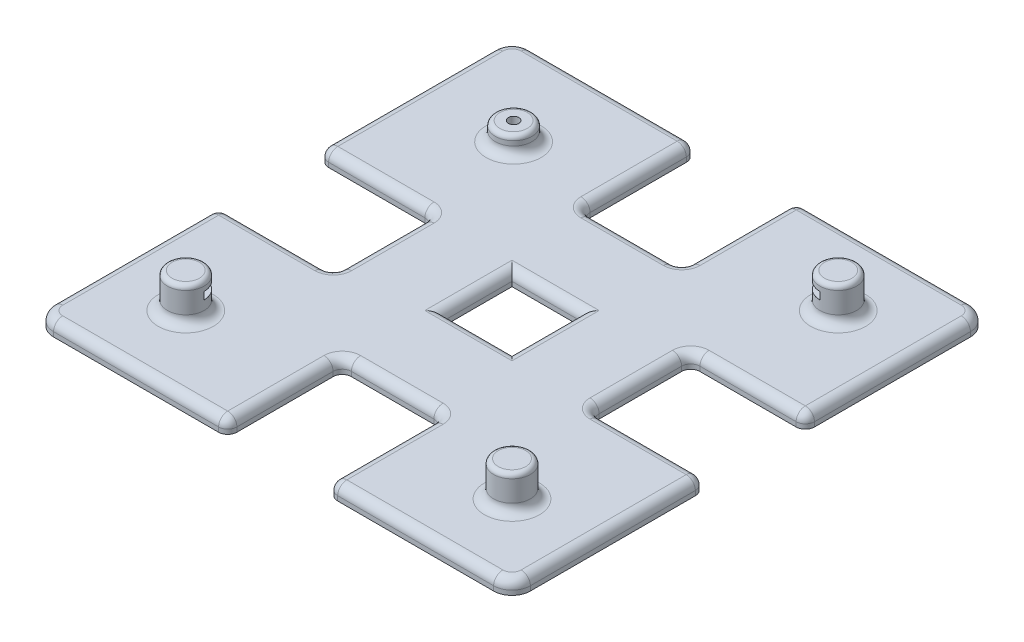
SolidWorks part; units mm, degrees
ref_plane "Front Plane" through (0, 0, 0) normal (0, 0, 1) x (1, 0, 0)
ref_plane "Top Plane" through (0, 0, 0) normal (0, 1, 0) x (1, 0, 0)
ref_plane "Right Plane" through (0, 0, 0) normal (1, 0, 0) x (0, 0, -1)
sketch "Sketch1" plane through (0, 0, 0) normal (0, 1, 0) x (1, 0, 0)
  line L0 (0, 51.97) -> (0, -51.97) construction
  line L1 (-51.97, 51.97) -> (51.97, 51.97)
  line L2 (-51.97, 51.97) -> (-51.97, -51.97)
  line L3 (-51.97, -51.97) -> (51.97, -51.97)
  line L4 (51.97, 51.97) -> (51.97, -51.97)
  line L5 (-51.97, 51.97) -> (51.97, -51.97) construction
  line L6 (-51.97, -51.97) -> (51.97, 51.97) construction
  line L7 (-51.97, 0) -> (51.97, 0) construction
  circle A0 centre (-31.7, 32.05) radius 1.1303
  circle A1 centre (31.7, 32.05) radius 1.1303 construction
  circle A2 centre (31.7, -32.05) radius 1.1303 construction
  circle A3 centre (-31.7, -32.05) radius 1.1303 construction
  point P0 (0, 0)
  dimension "D2" = 2.2606
  dimension "D1" = 103.94
  dimension "D3" = 63.4
  dimension "D4" = 64.1
extrude "Boss-Extrude1" add sketch "Sketch1" along normal blind 3
sketch "Sketch6" plane through (0, 3, 0) normal (0, 1, 0) x (1, 0, 0)
  line L0 (0, 51.97) -> (0, -51.97) construction
  line L1 (51.97, 51.97) -> (-51.97, 51.97) construction
  line L2 (-51.97, -51.97) -> (51.97, -51.97) construction
  line L3 (-51.97, 0) -> (51.97, 0) construction
  line L4 (-51.97, 51.97) -> (-51.97, -51.97) construction
  line L5 (51.97, -51.97) -> (51.97, 51.97) construction
  line L7 (-35.56, 35.56) -> (35.56, 35.56) construction
  line L8 (-35.56, 35.56) -> (-35.56, -35.56) construction
  line L9 (-35.56, -35.56) -> (35.56, -35.56) construction
  line L10 (35.56, 35.56) -> (35.56, -35.56) construction
  line L11 (-35.56, 35.56) -> (35.56, -35.56) construction
  line L12 (-35.56, -35.56) -> (35.56, 35.56) construction
  circle A0 centre (35.56, 35.56) radius 4
  circle A1 centre (35.56, -35.56) radius 4
  circle A2 centre (-35.56, -35.56) radius 4
  point P12 (0, 0)
  dimension "D2" = 8
  dimension "D1" = 71.12
extrude "Boss-Extrude3" add sketch "Sketch6" along normal blind 7.6
sketch "Sketch7" plane through (0, 0, 0) normal (0, 0, 1) x (1, 0, 0)
  line L1 (-35.56, 8.6) -> (35.56, 8.6)
  line L2 (-35.56, 8.6) -> (-35.56, 7)
  line L3 (-35.56, 7) -> (35.56, 7)
  line L4 (35.56, 8.6) -> (35.56, 7)
  line L5 (-35.56, 8.6) -> (35.56, 7) construction
  line L6 (-35.56, 7) -> (35.56, 8.6) construction
  line L8 (-51.97, 3) -> (51.97, 3) construction
  point P0 (0, 7.8)
  dimension "D1" = 1.6
  dimension "D2" = 4
  dimension "D3" = 71.12
extrude "Cut-Extrude4" cut sketch "Sketch7" against normal mid plane 71.12
sketch "Sketch2" plane through (0, 3, 0) normal (0, 1, 0) x (1, 0, 0)
  circle A0 centre (-31.7, 32.05) radius 1.1303 construction
  circle A4 centre (-31.7, 32.05) radius 1.1303
  circle A5 centre (31.5, 32.5) radius 1.9845 construction
  circle A6 centre (31.5, -32.5) radius 1.9845 construction
  circle A7 centre (-31.5, -32.5) radius 1.9845 construction
  circle A8 centre (-31.7, 32.05) radius 4
  circle A9 centre (31.5, 32.5) radius 4 construction
  circle A10 centre (31.5, -32.5) radius 4 construction
  circle A11 centre (-31.5, -32.5) radius 4 construction
  dimension "D1" = 8
extrude "Boss-Extrude2" add sketch "Sketch2" along normal blind 4
sketch "Sketch3" plane through (0, 3, 0) normal (0, 1, 0) x (1, 0, 0)
  line L0 (0, 51.97) -> (0, -51.97) construction
  line L1 (51.97, 51.97) -> (-51.97, 51.97) construction
  line L2 (-51.97, -51.97) -> (51.97, -51.97) construction
  line L3 (51.97, 0) -> (-51.97, 0) construction
  line L4 (10, 27) -> (-10, 27)
  line L5 (10, 27) -> (10, 51.97)
  line L6 (10, 51.97) -> (-10, 51.97)
  line L7 (-10, 27) -> (-10, 51.97)
  line L8 (10, 27) -> (-10, 51.97) construction
  line L9 (10, 51.97) -> (-10, 27) construction
  line L10 (51.97, -51.97) -> (51.97, 51.97) construction
  line L11 (-51.97, 51.97) -> (-51.97, -51.97) construction
  line L12 (10, -51.97) -> (-10, -51.97)
  line L13 (-10, -27) -> (-10, -51.97)
  line L14 (10, -27) -> (-10, -27)
  line L15 (10, -27) -> (10, -51.97)
  line L16 (-51.97, 10) -> (-51.97, -10)
  line L17 (27, 10) -> (51.97, 10)
  line L18 (27, 10) -> (27, -10)
  line L19 (27, -10) -> (51.97, -10)
  line L20 (51.97, 10) -> (51.97, -10)
  line L21 (27, 10) -> (51.97, -10) construction
  line L22 (27, -10) -> (51.97, 10) construction
  line L23 (-27, -10) -> (-51.97, -10)
  line L24 (-27, 10) -> (-27, -10)
  line L25 (-27, 10) -> (-51.97, 10)
  point P6 (0, 39.485)
  point P21 (39.485, 0)
  dimension "D1" = 54
  dimension "D2" = 20
extrude "Cut-Extrude1" cut sketch "Sketch3" against normal blind 10
sketch "Sketch4" plane through (0, 3, 0) normal (0, 1, 0) x (1, 0, 0)
  line L0 (-51.97, -10) -> (-51.97, -51.97) construction
  line L1 (-27, -10) -> (-51.97, -10)
  line L2 (-27, -10) -> (-27, -11.97)
  line L3 (-27, -11.97) -> (-51.97, -11.97)
  line L4 (-51.97, -10) -> (-51.97, -11.97)
  line L5 (10, -51.97) -> (51.97, -51.97) construction
  line L6 (10, -27) -> (11.97, -27)
  line L7 (10, -27) -> (10, -51.97)
  line L8 (10, -51.97) -> (11.97, -51.97)
  line L9 (11.97, -27) -> (11.97, -51.97)
  line L10 (51.97, 10) -> (51.97, 51.97) construction
  line L11 (27, 10) -> (51.97, 10)
  line L12 (27, 10) -> (27, 11.97)
  line L13 (27, 11.97) -> (51.97, 11.97)
  line L14 (51.97, 10) -> (51.97, 11.97)
  line L15 (-10, 51.97) -> (-51.97, 51.97) construction
  line L16 (-10, 27) -> (-11.97, 27)
  line L17 (-10, 27) -> (-10, 51.97)
  line L18 (-10, 51.97) -> (-11.97, 51.97)
  line L19 (-11.97, 27) -> (-11.97, 51.97)
  dimension "D1" = 1.97
extrude "Cut-Extrude2" cut sketch "Sketch4" against normal blind 10
sketch "Sketch5" plane through (0, 3, 0) normal (0, 1, 0) x (1, 0, 0)
  line L1 (7.5, 7.5) -> (-7.5, 7.5)
  line L2 (7.5, 7.5) -> (7.5, -7.5)
  line L3 (7.5, -7.5) -> (-7.5, -7.5)
  line L4 (-7.5, 7.5) -> (-7.5, -7.5)
  line L5 (7.5, 7.5) -> (-7.5, -7.5) construction
  line L6 (7.5, -7.5) -> (-7.5, 7.5) construction
  point P0 (0, 0)
  dimension "D1" = 15
extrude "Cut-Extrude3" cut sketch "Sketch5" against normal blind 10
fillet "Fillet3" radius 2 44 edges at (10, 3, -39.485) (30.985, 3, -51.97) (51.97, 3, -31.97) (39.485, 3, -11.97) (27, 3, -0.985) (39.485, 3, 10) (51.97, 3, 30.985) (31.97, 3, 51.97) (11.97, 3, 39.485) (0.985, 3, 27) (-10, 3, 39.485) (-30.985, 3, 51.97) (-51.97, 3, 31.97) (-39.485, 3, 11.97) (-27, 3, 0.985) (-39.485, 3, -10) (-51.97, 3, -30.985) (-31.97, 3, -51.97) (-11.97, 3, -39.485) (-0.985, 3, -27) (-11.97, 1.5, -51.97) (-27, 1.5, -10) (-27, 1.5, 11.97) (-51.97, 1.5, 11.97) (-10, 1.5, 51.97) (-10, 1.5, 27) (11.97, 1.5, 27) (11.97, 1.5, 51.97) (51.97, 1.5, 10) (27, 1.5, 10) (27, 1.5, -11.97) (51.97, 1.5, -11.97) (10, 1.5, -51.97) (10, 1.5, -27) (-11.97, 1.5, -27) (-51.97, 1.5, -10) (0, 3, 7.5) (7.5, 3, 0) (0, 3, -7.5) (-7.5, 3, 0) (35.56, 3, 39.56) (35.56, 3, -31.56) (-35.56, 3, 39.56) (-31.7, 3, -28.05)
fillet "Fillet4" radius 4 8 edges at (51.3842, 2.4142, 51.3842) (51.3842, 2.4142, -51.3842) (-51.3842, 2.4142, -51.3842) (-51.3842, 2.4142, 51.3842) (-51.97, 0.5, 51.97) (-51.97, 0.5, -51.97) (51.97, 0.5, -51.97) (51.97, 0.5, 51.97)
fillet "Fillet5" radius 1 4 edges at (-31.7, 7, -28.05) (35.56, 10.6, -31.56) (35.56, 10.6, 39.56) (-35.56, 10.6, 39.56)
sketch "Sketch8" plane through (0, 0, -35.56) normal (0, 0, 1) x (1, 0, 0)
  line L4 (31.56, 8.6) -> (31.56, 7)
  line L5 (31.56, 7) -> (35.56, 7)
  line L6 (35.56, 7) -> (35.56, 8.6)
  line L7 (35.56, 8.6) -> (31.56, 8.6)
  line L8 (31.56, 8.6) -> (31.56, 7)
  line L9 (31.56, 7) -> (35.56, 7)
  line L10 (35.56, 7) -> (35.56, 8.6)
  line L11 (35.56, 8.6) -> (31.56, 8.6)
  dimension "D1" = 0
extrude "Cut-Extrude5" cut sketch "Sketch8" against normal blind 10
